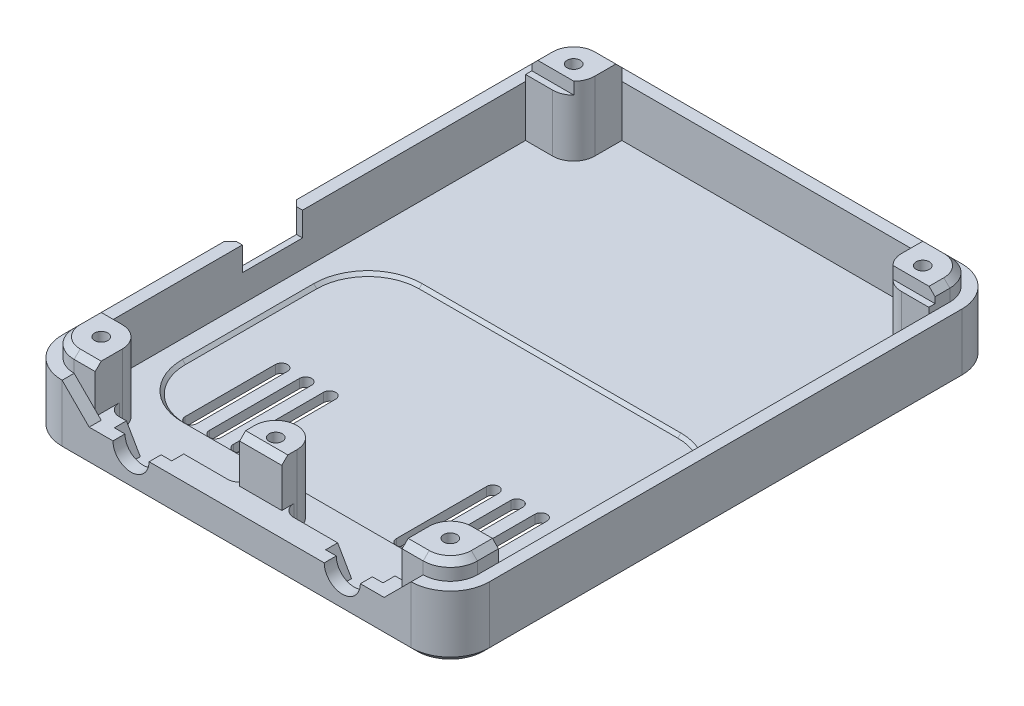
SolidWorks part; units mm, degrees
ref_plane "Front Plane" through (0, 0, 0) normal (0, 0, 1) x (1, 0, 0)
ref_plane "Top Plane" through (0, 0, 0) normal (0, 1, 0) x (1, 0, 0)
ref_plane "Right Plane" through (0, 0, 0) normal (1, 0, 0) x (0, 0, -1)
sketch "Sketch1" plane through (0, 0, 0) normal (0, 1, 0) x (1, 0, 0)
  line L0 (-33.8462, -25.5532) -> (31.1538, -25.5532)
  line L1 (-33.8462, 38.4468) -> (31.1538, 38.4468)
  line L2 (-33.8462, 38.4468) -> (-33.8462, 8.4468)
  line L3 (-33.8462, 8.4468) -> (31.1538, 8.4468)
  line L4 (31.1538, 38.4468) -> (31.1538, 8.4468)
  line L5 (-30.3462, 34.9468) -> (27.6538, 34.9468)
  line L6 (-30.3462, 34.9468) -> (-30.3462, 11.9468)
  line L7 (-30.3462, 11.9468) -> (27.6538, 11.9468)
  line L8 (27.6538, 34.9468) -> (27.6538, 11.9468)
  line L9 (-30.3462, 0.9468) -> (27.6538, 0.9468)
  line L10 (-30.3462, 0.9468) -> (-30.3462, -22.0532)
  line L11 (-33.8462, 4.4468) -> (31.1538, 4.4468)
  line L12 (-33.8462, 4.4468) -> (-33.8462, -25.5532)
  line L13 (-30.3462, -22.0532) -> (27.6538, -22.0532)
  line L14 (31.1538, 4.4468) -> (31.1538, -25.5532)
  line L15 (27.6538, 0.9468) -> (27.6538, -22.0532)
  line L16 (-37.9161, 25.3468) -> (-35.3276, 25.3468)
  line L17 (7.5538, 7.5472) -> (7.5538, 6.2645)
  line L18 (20.1538, 7.5472) -> (20.1538, 6.2645)
  dimension "D1" = 65
  dimension "D2" = 30
  dimension "D3" = 58
  dimension "D4" = 23
  dimension "D5" = 3.5
  dimension "D6" = 3.5
  dimension "D7" = 65
  dimension "D8" = 30
  dimension "D9" = 58
  dimension "D10" = 23
  dimension "D11" = 3.5
  dimension "D12" = 3.5
  dimension "D13" = 4
  dimension "D14" = 16.9
  dimension "D15" = 41.4
  dimension "D16" = 54
sketch "Sketch2" plane through (0, 0, 0) normal (0, 1, 0) x (1, 0, 0)
  line L0 (-33.8462, 38.4468) -> (-33.8462, 8.4468) construction
  line L1 (-30.3462, 39.4468) -> (27.6538, 39.4468)
  line L2 (-34.8462, 34.9468) -> (-34.8462, -43.5532)
  line L3 (-30.3462, -48.0532) -> (27.6538, -48.0532)
  line L4 (32.1538, 34.9468) -> (32.1538, -43.5532)
  line L5 (-33.8462, 38.4468) -> (31.1538, 38.4468) construction
  line L6 (31.1538, 38.4468) -> (31.1538, 8.4468) construction
  line L7 (-30.3462, 41.4468) -> (27.6538, 41.4468)
  line L8 (34.1538, 34.9468) -> (34.1538, -43.5532)
  line L9 (-30.3462, -50.0532) -> (27.6538, -50.0532)
  line L10 (-36.8462, 34.9468) -> (-36.8462, -43.5532)
  line L11 (-34.8462, 39.4468) -> (32.1538, 39.4468) construction
  line L12 (-34.8462, 39.4468) -> (-34.8462, -48.0532) construction
  line L13 (-36.8462, 41.4468) -> (-36.8462, -50.0532) construction
  line L14 (-36.8462, 41.4468) -> (34.1538, 41.4468) construction
  line L15 (32.1538, 39.4468) -> (32.1538, -48.0532) construction
  line L16 (34.1538, 41.4468) -> (34.1538, -50.0532) construction
  line L17 (-36.8462, -50.0532) -> (34.1538, -50.0532) construction
  line L18 (-34.8462, -48.0532) -> (32.1538, -48.0532) construction
  arc A0 (-30.3462, 39.4468) -> (-34.8462, 34.9468) centre (-30.3462, 34.9468) ccw
  arc A1 (-36.8462, 34.9468) -> (-30.3462, 41.4468) centre (-30.3462, 34.9468) cw
  arc A2 (32.1538, 34.9468) -> (27.6538, 39.4468) centre (27.6538, 34.9468) ccw
  arc A3 (34.1538, 34.9468) -> (27.6538, 41.4468) centre (27.6538, 34.9468) ccw
  arc A4 (27.6538, -50.0532) -> (34.1538, -43.5532) centre (27.6538, -43.5532) ccw
  arc A5 (-36.8462, -43.5532) -> (-30.3462, -50.0532) centre (-30.3462, -43.5532) ccw
  arc A6 (27.6538, -48.0532) -> (32.1538, -43.5532) centre (27.6538, -43.5532) ccw
  arc A7 (-30.3462, -48.0532) -> (-34.8462, -43.5532) centre (-30.3462, -43.5532) cw
  dimension "D6" = 4.5
  dimension "D7" = 6.5
  dimension "D8" = 4.5
  dimension "D9" = 6.5
  dimension "D10" = 6.5
  dimension "D11" = 4.5
  dimension "D1" = 1
  dimension "D2" = 1
  dimension "D3" = 1
  dimension "D4" = 87.5
  dimension "D5" = 2
extrude "Boss-Extrude1" add sketch "Sketch2" along normal blind 10.5
sketch "Sketch3" plane through (0, 0, 0) normal (0, 1, 0) x (1, 0, 0)
  line L0 (-30.3462, -48.0532) -> (27.6538, -48.0532)
  line L1 (-30.3462, 39.4468) -> (27.6538, 39.4468)
  line L2 (-34.8462, 34.9468) -> (-34.8462, -43.5532)
  line L4 (32.1538, 34.9468) -> (32.1538, -43.5532)
  arc A0 (27.6538, -48.0532) -> (32.1538, -43.5532) centre (27.6538, -43.5532) ccw
  arc A1 (-34.8462, -43.5532) -> (-30.3462, -48.0532) centre (-30.3462, -43.5532) ccw
  arc A2 (32.1538, 34.9468) -> (27.6538, 39.4468) centre (27.6538, 34.9468) ccw
  arc A3 (-30.3462, 39.4468) -> (-34.8462, 34.9468) centre (-30.3462, 34.9468) ccw
  point P15 (-34.8462, 39.4468)
  dimension "D1" = 4.5
  dimension "D2" = 87.5
extrude "Boss-Extrude2" add sketch "Sketch3" along normal blind 2
sketch "Sketch6" plane through (0, 2, 0) normal (0, 1, 0) x (1, 0, 0)
  line L3 (-34.8462, 34.9468) -> (-34.8462, -43.5532) construction
  line L5 (-26.8462, 34.9468) -> (-26.8462, 39.4468)
  line L6 (27.6538, 39.4468) -> (-30.3462, 39.4468) construction
  line L7 (-26.8462, 39.4468) -> (-30.3462, 39.4468)
  line L8 (-30.3462, 31.4468) -> (-34.8462, 31.4468)
  line L9 (-34.8462, 31.4468) -> (-34.8462, 34.9468)
  line L10 (24.1538, 34.9468) -> (24.1538, 39.4468)
  line L11 (24.1538, 39.4468) -> (27.6538, 39.4468)
  line L12 (27.6538, 31.4468) -> (32.1538, 31.4468)
  line L13 (32.1538, -43.5532) -> (32.1538, 34.9468) construction
  line L14 (32.1538, 31.4468) -> (32.1538, 34.9468)
  arc A0 (-30.3462, 31.4468) -> (-26.8462, 34.9468) centre (-30.3462, 34.9468) ccw
  arc A1 (24.1538, 34.9468) -> (27.6538, 31.4468) centre (27.6538, 34.9468) ccw
  arc A4 (-30.3462, 39.4468) -> (-34.8462, 34.9468) centre (-30.3462, 34.9468) ccw
  arc A5 (32.1538, 34.9468) -> (27.6538, 39.4468) centre (27.6538, 34.9468) ccw
  dimension "D1" = 4.5
  dimension "D2" = 4.5
extrude "Boss-Extrude4" add sketch "Sketch6" along normal blind 11.5
sketch "Sketch7" plane through (0, 0, 50.0532) normal (0, 0, 1) x (1, 0, 0)
  line L0 (27.6538, 10.5) -> (-30.3462, 10.5)
  line L2 (16.2046, 6) -> (16.2046, 3) construction
  line L3 (-18.8969, 6) -> (-18.8969, 3) construction
  line L4 (-1.3462, 10.5) -> (-1.3462, 13.2512) construction
  line L5 (-30.3462, 10.5) -> (27.6538, 10.5) construction
  line L20 (27.6538, 10.5) -> (23.1538, 6)
  line L21 (23.1538, 6) -> (19.2046, 6)
  line L22 (13.2046, 6) -> (-15.8969, 6)
  line L23 (-25.8462, 6) -> (-21.8969, 6)
  line L24 (-30.3462, 10.5) -> (-25.8462, 6)
  arc A0 (-21.8969, 6) -> (-15.8969, 6) centre (-18.8969, 6) ccw
  arc A1 (13.2046, 6) -> (19.2046, 6) centre (16.2046, 6) ccw
  dimension "D3" = 45
  dimension "D1" = 4.5
  dimension "D4" = 3
  dimension "D5" = 3
  dimension "D2" = 45
  dimension "D6" = 4.5
  dimension "D7" = 4.5
sketch "Sketch8" plane through (0, 2, 0) normal (0, 1, 0) x (1, 0, 0)
  line L0 (-4.8462, -43.5532) -> (-4.8462, -48.0532)
  line L2 (-30.3462, -48.0532) -> (27.6538, -48.0532) construction
  line L4 (-4.8462, -48.0532) -> (2.1538, -48.0532)
  line L5 (2.1538, -48.0532) -> (2.1538, -43.5532)
  line L9 (32.1538, -40.0532) -> (32.1538, -43.5532)
  line L10 (27.6538, -40.0532) -> (32.1538, -40.0532)
  line L11 (24.1538, -48.0532) -> (27.6538, -48.0532)
  line L12 (24.1538, -43.5532) -> (24.1538, -48.0532)
  line L13 (-34.8462, -40.0532) -> (-34.8462, -43.5532)
  line L14 (-30.3462, -40.0532) -> (-34.8462, -40.0532)
  line L15 (-26.8462, -48.0532) -> (-30.3462, -48.0532)
  line L16 (-26.8462, -43.5532) -> (-26.8462, -48.0532)
  arc A0 (2.1538, -43.5532) -> (-4.8462, -43.5532) centre (-1.3462, -43.5532) ccw
  arc A4 (32.1538, -43.5532) -> (27.6538, -48.0532) centre (27.6538, -43.5532) cw
  arc A5 (-30.3462, -48.0532) -> (-34.8462, -43.5532) centre (-30.3462, -43.5532) cw
  arc A6 (24.1538, -43.5532) -> (27.6538, -40.0532) centre (27.6538, -43.5532) cw
  arc A7 (-30.3462, -40.0532) -> (-26.8462, -43.5532) centre (-30.3462, -43.5532) cw
extrude "Boss-Extrude6" add sketch "Sketch8" along normal up to surface (11.5 mm away) up to face at (-30.714, 13.5, -35.3147)
extrude "Cut-Extrude1" cut sketch "Sketch7" against normal up to vertex (2 mm away) up to point (-15.8462, 10.5, 48.0532)
sketch "Sketch9" plane through (-36.8462, 0, 0) normal (-1, 0, 0) x (0, 0, 1)
  line L1 (15.6113, 10.5) -> (5.6113, 10.5)
  line L2 (15.6113, 10.5) -> (15.6113, 6.5)
  line L3 (15.6113, 6.5) -> (5.6113, 6.5)
  line L4 (5.6113, 10.5) -> (5.6113, 6.5)
  line L5 (15.6113, 10.5) -> (5.6113, 6.5) construction
  line L6 (15.6113, 6.5) -> (5.6113, 10.5) construction
  point P0 (10.6113, 8.5)
  dimension "D1" = 10
  dimension "D2" = 4
extrude "Cut-Extrude2" cut sketch "Sketch9" against normal up to next
chamfer "Chamfer1" distance 1 angle 45 3 edges at (-36.8462, 8.5, 5.6113) (-36.8462, 8.5, 15.6113) (-36.8462, 6.5, 10.6113)
chamfer "Chamfer2" distance 1 angle 45 8 edges at (-36.8462, 0, 4.3032) (-34.9423, 0, 48.1493) (-34.9423, 0, -39.543) (-1.3462, 0, 50.0532) (-1.3462, 0, -41.4468) (32.25, 0, 48.1493) (32.25, 0, -39.543) (34.1538, 0, 4.3032)
sketch "Sketch19" plane through (0, 0, 48.0532) normal (0, 0, -1) x (-1, 0, 0)
  line L0 (24.6458, 6) -> (23.6607, 6)
  line L1 (14.1331, 6) -> (16.515, 1.8744)
  line L2 (16.515, 1.8744) -> (21.2788, 1.8744)
  line L3 (21.2788, 1.8744) -> (23.6607, 6)
  line L4 (-11.4408, 6) -> (-10.4558, 6)
  line L5 (-20.9684, 6) -> (-21.9535, 6)
  line L6 (24.6458, 6) -> (26.8462, 6)
  line L7 (-20.9684, 6) -> (-18.5865, 1.8744)
  line L8 (-18.5865, 1.8744) -> (-13.8227, 1.8744)
  line L9 (-13.8227, 1.8744) -> (-11.4408, 6)
  line L10 (26.8462, 7) -> (26.8462, 2) construction
  line L11 (26.8462, 6) -> (26.8462, 2)
  line L12 (26.8462, 2) -> (21.3513, 2)
  line L13 (13.1481, 6) -> (14.1331, 6)
  line L14 (26.8462, 2) -> (4.8462, 2) construction
  line L15 (22.4698, 8.0628) -> (21.3151, 10.0628) [skipped]
  line L16 (16.3625, 9.8613) -> (15.2078, 7.8613) [skipped]
  line L17 (20.9737, 10.1256) -> (16.3549, 10.1256) [skipped]
  line L18 (-12.6318, 8.0628) -> (-13.7865, 10.0628) [skipped]
  line L19 (-16.2046, 10.1256) -> (-18.514, 10.1256) [skipped]
  line L20 (-18.7391, 9.8613) -> (-19.8938, 7.8613) [skipped]
  line L21 (13.1481, 6) -> (-10.4558, 6)
  line L22 (-21.9535, 6) -> (-24.1538, 6)
  line L23 (-24.1538, 7) -> (-24.1538, 2) construction
  line L24 (-24.1538, 6) -> (-24.1538, 2)
  line L25 (-24.1538, 2) -> (-18.659, 2)
  line L26 (-13.7502, 2) -> (16.4425, 2)
  arc A0 (15.3241, 3.9372) -> (22.4698, 3.9372) centre (18.8969, 6) ccw construction
  arc A1 (-19.7775, 3.9372) -> (-12.6318, 3.9372) centre (-16.2046, 6) ccw construction
extrude "Boss-Extrude7" add sketch "Sketch19" along normal blind 2
sketch "Sketch21" plane through (0, 13.5, 0) normal (0, 1, 0) x (1, 0, 0)
  line L0 (-34.8462, 34.9468) -> (-34.8462, 31.4468) construction
  line L1 (-34.8462, 32.4905) -> (32.1538, 32.4905)
  line L2 (-34.8462, 32.4905) -> (-34.8462, 31.4468)
  line L3 (-34.8462, 31.4468) -> (32.1538, 31.4468)
  line L4 (32.1538, 32.4905) -> (32.1538, 31.4468)
extrude "Cut-Extrude4" cut sketch "Sketch21" against normal blind 2
sketch "Sketch22" plane through (0, 2, 0) normal (0, 1, 0) x (1, 0, 0)
  line L0 (-34.8462, 31.4468) -> (-34.8462, -40.0532) construction
  line L1 (-22.8462, 3.2594) -> (20.1538, 3.2594)
  line L2 (-32.8462, -6.7406) -> (-32.8462, -28.5682)
  line L3 (-22.8462, -38.5682) -> (20.1538, -38.5682)
  line L4 (30.1538, -6.7406) -> (30.1538, -28.5682)
  line L5 (32.1538, -40.0532) -> (32.1538, 31.4468) construction
  arc A0 (-22.8462, -38.5682) -> (-32.8462, -28.5682) centre (-22.8462, -28.5682) cw
  arc A1 (20.1538, -38.5682) -> (30.1538, -28.5682) centre (20.1538, -28.5682) ccw
  arc A2 (20.1538, 3.2594) -> (30.1538, -6.7406) centre (20.1538, -6.7406) cw
  arc A3 (-22.8462, 3.2594) -> (-32.8462, -6.7406) centre (-22.8462, -6.7406) ccw
  dimension "D3" = 10
  dimension "D1" = 2
  dimension "D2" = 2
extrude "Cut-Extrude5" cut sketch "Sketch22" against normal blind 0.5
chamfer "Chamfer4" distance 1.5 angle 45 8 edges at (-1.3462, 1.5, 38.5682) (27.2249, 1.5, 35.6392) (-29.9172, 1.5, 35.6392) (30.1538, 1.5, 17.6544) (-32.8462, 1.5, 17.6544) (27.2249, 1.5, -0.3305) (-29.9172, 1.5, -0.3305) (-1.3462, 1.5, -3.2594)
chamfer "Chamfer5" distance 1 angle 45 3 edges at (32.1538, 13.5, -33.7187) (25.9038, 13.5, -39.4468) (30.8358, 13.5, -38.1288)
chamfer "Chamfer6" distance 1 angle 45 3 edges at (-28.5962, 13.5, -39.4468) (-34.8462, 13.5, -33.7187) (-33.5281, 13.5, -38.1288)
chamfer "Chamfer7" distance 1 angle 45 6 edges at (25.9038, 13.5, 48.0532) (32.1538, 13.5, 41.8032) (30.8358, 13.5, 46.7351) (-34.8462, 13.5, 41.8032) (-28.5962, 13.5, 48.0532) (-33.5281, 13.5, 46.7351)
hole_wizard "Ø2.2 (2.2) Diameter Hole1" positions "Sketch24" profile "Sketch25" hole size "Ø2.2" standard "ANSI Metric"
sketch "Sketch24" plane through (0, 13.5, 0) normal (0, 1, 0) x (1, 0, 0)
  point P0 (-30.3462, -43.5532)
  point P4 (27.6538, -43.5532)
  point P10 (27.6538, 34.9468)
  point P14 (-30.3462, 34.9468)
  point P17 (-1.3462, -43.5532)
sketch "Sketch25" plane through (-30.3462, 13.5, 43.5532) normal (1, 0, 0) x (0, 0, 1)
  line L0 (0, 0) -> (0, 12.1609)
  line L1 (0, 12.1609) -> (1.1, 11.5)
  line L2 (1.1, 11.5) -> (1.1, 0)
  line L5 (1.1, 0) -> (0, 0)
  line L10 (0, 12.1609) -> (-1.1, 11.5) construction
  line L11 (0, -6.35) -> (0, 107.95) construction
  dimension "Hole Dia." = 2.2
  dimension "Hole Depth" = 11.5
  dimension "Drill Angle" = 118
sketch "Sketch27" plane through (0, 13.5, 0) normal (0, 1, 0) x (1, 0, 0)
  line L1 (-4.8462, -46.0532) -> (2.1538, -46.0532)
  line L2 (-4.8462, -46.0532) -> (-4.8462, -48.0532)
  line L3 (-4.8462, -48.0532) -> (2.1538, -48.0532)
  line L4 (2.1538, -46.0532) -> (2.1538, -48.0532)
extrude "Cut-Extrude6" cut sketch "Sketch27" against normal up to surface (7.5 mm away) up to face at (-1.3462, 6, 47.7198)
fillet "Fillet1" radius 2 4 edges at (-26.8462, 4, 46.0532) (2.1538, 4, 46.0532) (-4.8462, 4, 46.0532) (24.1538, 4, 46.0532)
chamfer "Chamfer8" distance 1 angle 45 1 edges at (-1.3462, 13.5, 46.0532)
sketch "Sketch28" plane through (0, 0, 0) normal (0, -1, 0) x (1, 0, 0)
  line L0 (-18.8969, 36.0532) -> (-18.8969, 21.0532) construction
  line L1 (-17.8969, 36.0532) -> (-17.8969, 21.0532)
  line L2 (-19.8969, 36.0532) -> (-19.8969, 21.0532)
  line L3 (-18.8969, 48.0532) -> (-18.8969, 15.8895) construction
  line L4 (-21.3513, 48.0532) -> (-16.4425, 48.0532) construction
  line L5 (-15.8969, 50.0532) -> (-21.8969, 50.0532) construction
  line L6 (-22.8969, 36.0532) -> (-22.8969, 21.0532) construction
  line L7 (-21.8969, 36.0532) -> (-21.8969, 21.0532)
  line L8 (-23.8969, 36.0532) -> (-23.8969, 21.0532)
  line L9 (-14.8969, 36.0532) -> (-14.8969, 21.0532) construction
  line L10 (-13.8969, 36.0532) -> (-13.8969, 21.0532)
  line L11 (-15.8969, 36.0532) -> (-15.8969, 21.0532)
  line L12 (16.2046, 48.0532) -> (16.2046, 15.8895) construction
  line L13 (16.2046, 36.0532) -> (16.2046, 21.0532) construction
  line L14 (17.2046, 36.0532) -> (17.2046, 21.0532)
  line L15 (15.2046, 36.0532) -> (15.2046, 21.0532)
  line L16 (12.2046, 36.0532) -> (12.2046, 21.0532) construction
  line L17 (13.2046, 36.0532) -> (13.2046, 21.0532)
  line L18 (11.2046, 36.0532) -> (11.2046, 21.0532)
  line L19 (20.2046, 36.0532) -> (20.2046, 21.0532) construction
  line L20 (21.2046, 36.0532) -> (21.2046, 21.0532)
  line L21 (19.2046, 36.0532) -> (19.2046, 21.0532)
  arc A0 (-17.8969, 36.0532) -> (-19.8969, 36.0532) centre (-18.8969, 36.0532) ccw
  arc A1 (-19.8969, 21.0532) -> (-17.8969, 21.0532) centre (-18.8969, 21.0532) ccw
  arc A2 (-21.8969, 36.0532) -> (-23.8969, 36.0532) centre (-22.8969, 36.0532) ccw
  arc A3 (-23.8969, 21.0532) -> (-21.8969, 21.0532) centre (-22.8969, 21.0532) ccw
  arc A4 (-13.8969, 36.0532) -> (-15.8969, 36.0532) centre (-14.8969, 36.0532) ccw
  arc A5 (-15.8969, 21.0532) -> (-13.8969, 21.0532) centre (-14.8969, 21.0532) ccw
  arc A6 (17.2046, 36.0532) -> (15.2046, 36.0532) centre (16.2046, 36.0532) ccw
  arc A7 (15.2046, 21.0532) -> (17.2046, 21.0532) centre (16.2046, 21.0532) ccw
  arc A8 (13.2046, 36.0532) -> (11.2046, 36.0532) centre (12.2046, 36.0532) ccw
  arc A9 (11.2046, 21.0532) -> (13.2046, 21.0532) centre (12.2046, 21.0532) ccw
  arc A10 (21.2046, 36.0532) -> (19.2046, 36.0532) centre (20.2046, 36.0532) ccw
  arc A11 (19.2046, 21.0532) -> (21.2046, 21.0532) centre (20.2046, 21.0532) ccw
  point P2 (-18.8969, 28.5532)
  point P11 (-18.8969, 50.0532)
  point P18 (-22.8969, 28.5532)
  point P24 (-14.8969, 28.5532)
  point P30 (16.2046, 28.5532)
  point P40 (12.2046, 28.5532)
  point P46 (20.2046, 28.5532)
  dimension "D1" = 14
  dimension "D2" = 2
  dimension "D3" = 2
extrude "Cut-Extrude7" cut sketch "Sketch28" against normal through all
